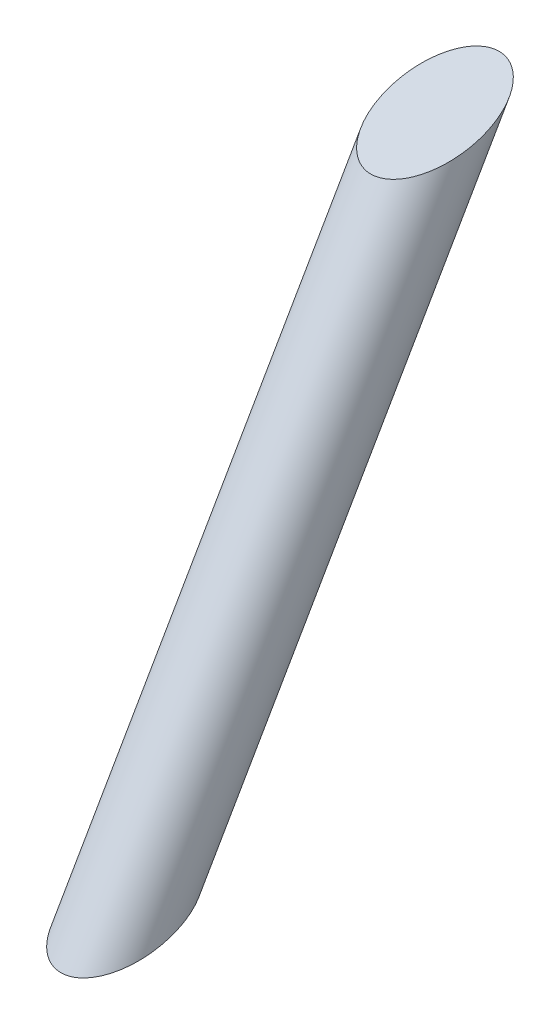
SolidWorks part; units mm, degrees
ref_plane "Ön Düzlem" through (0, 0, 0) normal (0, 0, 1) x (1, 0, 0)
ref_plane "Üst Düzlem" through (0, 0, 0) normal (0, 1, 0) x (1, 0, 0)
ref_plane "Sağ Düzlem" through (0, 0, 0) normal (1, 0, 0) x (0, 0, -1)
sketch "Çizim1" plane through (0, 0, 0) normal (1, 0, 0) x (0, 0, -1)
  line L0 (-24.8276, -44.2666) -> (55.1724, 94.2975)
  dimension "D1" = 160
revolve "Döndür-İnce1" add sketch "Çizim1" angle 360 about L0 wall 10
sketch "Çizim3" plane through (0, 0, 0) normal (1, 0, 0) x (0, 0, -1)
  line L0 (63.8326, 89.2975) -> (46.5121, 99.2975)
  line L1 (63.8326, 89.2975) -> (46.5121, 99.2975) construction
  line L2 (46.5121, 99.2975) -> (35.3318, 79.9326)
  line L3 (46.5121, 99.2975) -> (-33.4879, -39.2666) construction
  line L4 (35.3318, 79.9326) -> (63.8326, 89.2975)
  line L5 (-33.4879, -39.2666) -> (-16.1674, -49.2666)
  line L6 (-16.1674, -49.2666) -> (-4.987, -29.9017)
  line L7 (-16.1674, -49.2666) -> (63.8326, 89.2975) construction
  line L8 (-4.987, -29.9017) -> (-33.4879, -39.2666)
  dimension "D1" = 30
  dimension "D2" = 30
extrude "Kes-Ekstrüzyon1" cut sketch "Çizim3" against normal blind 10 and the other way blind 10
